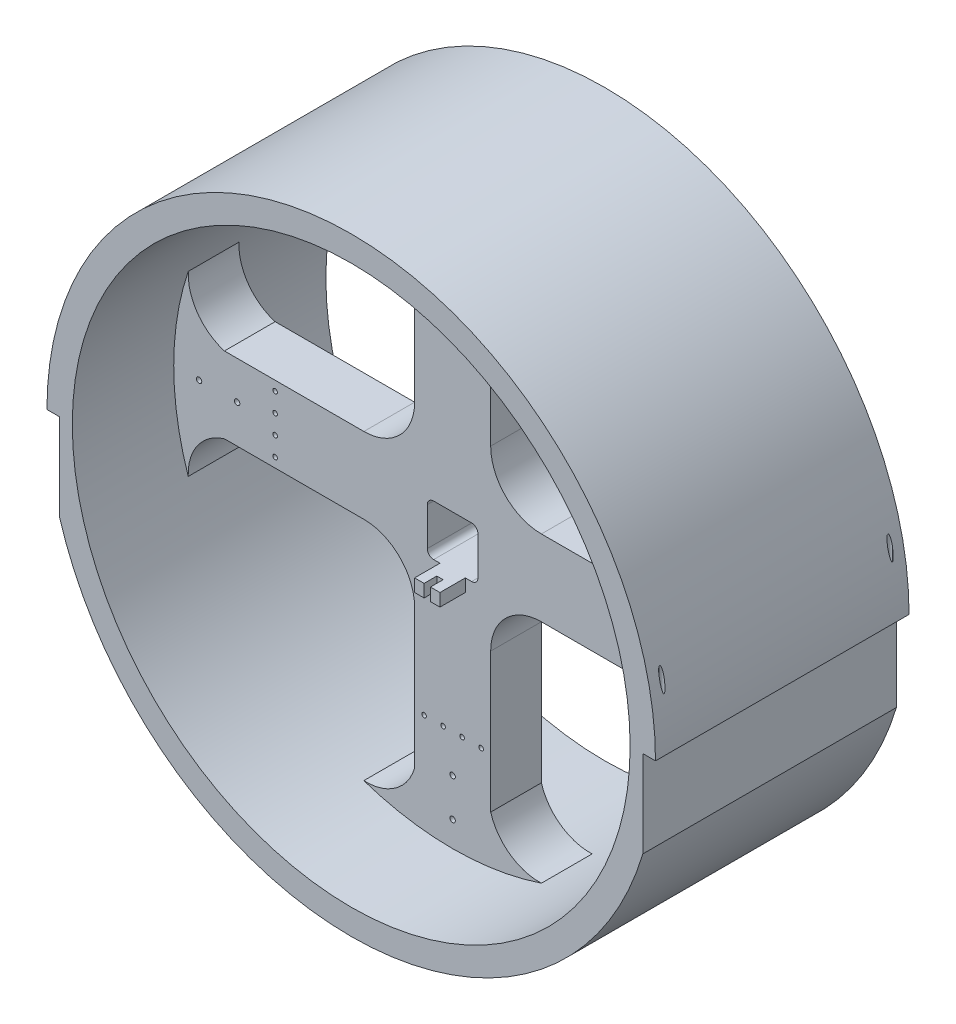
SolidWorks part; units mm, degrees
material "6061 Alloy"
ref_plane "Front Plane" through (0, 0, 0) normal (0, 0, 1) x (1, 0, 0)
ref_plane "Top Plane" through (0, 0, 0) normal (0, 1, 0) x (1, 0, 0)
ref_plane "Right Plane" through (0, 0, 0) normal (1, 0, 0) x (0, 0, -1)
sketch "Sketch1" plane through (0, 0, 0) normal (0, 0, 1) x (1, 0, 0)
  circle A0 centre (0, 0) radius 152.4
  circle A1 centre (0, 0) radius 139.7
  dimension "D1" = 304.8
  dimension "D2" = 279.4
extrude "Boss-Extrude1" add sketch "Sketch1" along normal mid plane 127
sketch "Sketch2" plane through (0, 0, 0) normal (0, 0, 1) x (1, 0, 0)
  line L0 (-114.3, 19.05) -> (-138.7192, 19.05)
  line L1 (-147.1918, -19.05) -> (147.1918, -19.05)
  line L2 (-147.1918, -19.05) -> (-147.1918, 19.05)
  line L3 (-147.1918, 19.05) -> (147.1918, 19.05)
  line L4 (147.1918, -19.05) -> (147.1918, 19.05)
  line L5 (-147.1918, -19.05) -> (147.1918, 19.05) construction
  line L6 (-147.1918, 19.05) -> (147.1918, -19.05) construction
  line L7 (19.05, -143.9568) -> (-19.05, -143.9568)
  line L8 (19.05, -143.9568) -> (19.05, 143.9568)
  line L9 (19.05, 143.9568) -> (-19.05, 143.9568)
  line L10 (-19.05, -143.9568) -> (-19.05, 143.9568)
  line L11 (19.05, -143.9568) -> (-19.05, 143.9568) construction
  line L12 (19.05, 143.9568) -> (-19.05, -143.9568) construction
  line L15 (-44.45, 19.05) -> (-19.05, 19.05)
  line L16 (-19.05, 44.45) -> (-19.05, 19.05)
  line L17 (-132.4254, 44.4927) -> (-143.3503, 19.05)
  line L18 (-143.3503, 19.05) -> (-138.7192, 19.05)
  line L19 (-138.7192, 19.05) -> (-143.3503, 19.05)
  line L20 (-19.05, 114.3) -> (-19.05, 143.9568)
  line L21 (-44.45, 132.4398) -> (-19.05, 143.9568)
  line L22 (44.45, 19.05) -> (19.05, 19.05)
  line L23 (19.05, 44.45) -> (19.05, 19.05)
  line L24 (19.05, 143.3503) -> (19.05, 138.7192)
  line L25 (19.05, 114.3) -> (19.05, 138.7192)
  line L26 (44.4927, 132.4254) -> (19.05, 143.3503)
  line L27 (114.3, 19.05) -> (143.9568, 19.05)
  line L28 (132.4398, 44.45) -> (143.9568, 19.05)
  line L29 (19.05, -44.45) -> (19.05, -19.05)
  line L30 (44.45, -19.05) -> (19.05, -19.05)
  line L31 (143.3503, -19.05) -> (138.7192, -19.05)
  line L32 (114.3, -19.05) -> (138.7192, -19.05)
  line L33 (132.4254, -44.4927) -> (143.3503, -19.05)
  line L34 (19.05, -114.3) -> (19.05, -143.9568)
  line L35 (44.45, -132.4398) -> (19.05, -143.9568)
  line L36 (-44.45, -19.05) -> (-19.05, -19.05)
  line L37 (-19.05, -44.45) -> (-19.05, -19.05)
  line L38 (-19.05, -143.3503) -> (-19.05, -138.7192)
  line L39 (-19.05, -114.3) -> (-19.05, -138.7192)
  line L40 (-44.4927, -132.4254) -> (-19.05, -143.3503)
  line L41 (-114.3, -19.05) -> (-143.9568, -19.05)
  line L42 (-132.4398, -44.45) -> (-143.9568, -19.05)
  arc A1 (-44.45, 19.05) -> (-19.05, 44.45) centre (-44.45, 44.45) ccw
  arc A2 (-114.3, 19.05) -> (-132.4254, 44.4927) centre (-107.0492, 43.3931) cw
  circle A3 centre (0, 0) radius 139.7 construction
  arc A5 (-19.05, 114.3) -> (-44.45, 132.4398) centre (-43.3968, 107.0616) ccw
  arc A6 (19.05, 44.45) -> (44.45, 19.05) centre (44.45, 44.45) ccw
  arc A7 (19.05, 114.3) -> (44.4927, 132.4254) centre (43.3931, 107.0492) cw
  arc A8 (114.3, 19.05) -> (132.4398, 44.45) centre (107.0616, 43.3968) ccw
  arc A9 (44.45, -19.05) -> (19.05, -44.45) centre (44.45, -44.45) ccw
  arc A10 (114.3, -19.05) -> (132.4254, -44.4927) centre (107.0492, -43.3931) cw
  arc A11 (19.05, -114.3) -> (44.45, -132.4398) centre (43.3968, -107.0616) ccw
  arc A12 (-19.05, -44.45) -> (-44.45, -19.05) centre (-44.45, -44.45) ccw
  arc A13 (-19.05, -114.3) -> (-44.4927, -132.4254) centre (-43.3931, -107.0492) cw
  arc A14 (-114.3, -19.05) -> (-132.4398, -44.45) centre (-107.0616, -43.3968) ccw
  point P0 (0, 0)
  point P6 (0, 0)
  point P67 (0, 0)
  dimension "D3" = 25.4
  dimension "D5" = 25.4
  dimension "D1" = 38.1
  dimension "D2" = 38.1
  dimension "D4" = 114.3
  dimension "D6" = 114.3
  dimension "D7" = 4
extrude "Boss-Extrude2" add sketch "Sketch2" along normal mid plane 25.4 contours L1 L10 L3 L2 | L10 L1 L8 L3 | L10 L3 L8 L9 | L8 L1 L4 L3 | L10 L7 L8 L1 | A14 L1 L42 | L10 A13 L40 | A11 L8 L35 | A9 L1 L8 | L1 A10 L33 | A8 L3 L28 | L8 A7 L26 | A5 L10 L21 | L0 A2 L17 L3 | A1 L3 L10 | A6 L8 L3 | A12 L10 L1 region at (-83.1209, 0, 0) region at (-132.2215, 26.1932, 0) region at (-24.7235, 24.7235, 0) region at (0, 81.5034, 0) region at (0, 0, 0) region at (24.7235, 24.7235, 0) region at (83.1209, 0, 0) region at (-24.7235, -24.7235, 0) region at (0, -81.5034, 0) region at (-26.2233, 132.4495, 0) region at (24.7235, -24.7235, 0) region at (-132.4495, -26.2233, 0) region at (132.4495, 26.2233, 0) region at (26.1932, 132.2215, 0) region at (-26.1932, -132.2215, 0) region at (132.2215, -26.1932, 0) region at (26.2233, -132.4495, 0)
sketch "Sketch4" plane through (0, 0, 0) normal (0, 0, 1) x (1, 0, 0)
  line L0 (-12.7, -19.05) -> (-12.7, 6.35)
  line L5 (-12.7, -19.05) -> (12.7, -19.05)
  line L6 (-12.7, 6.35) -> (12.7, 6.35)
  line L7 (12.7, -19.05) -> (12.7, 6.35)
  line L8 (-12.7, -19.05) -> (12.7, 6.35) construction
  line L9 (-12.7, 6.35) -> (12.7, -19.05) construction
  point P1 (0, -6.35)
  dimension "D1" = 25.4
  dimension "D2" = 25.4
  dimension "D3" = 0
  dimension "D4" = 6.35
extrude "Cut-Extrude3" cut sketch "Sketch4" against normal through all both and the other way through all
sketch "Sketch8" plane through (0, 0, 63.5) normal (0, 0, 1) x (1, 0, 0)
  line L0 (-146.05, 0) -> (-163.2527, 0)
  line L1 (-146.05, 0) -> (-146.05, -50.8)
  line L2 (-163.2527, 0) -> (-163.2527, -50.8)
  line L3 (-146.05, -50.8) -> (-163.2527, -50.8)
  circle A0 centre (0, 0) radius 152.4 construction
  dimension "D1" = 50.8
  dimension "D2" = 146.05
extrude "Cut-Extrude5" cut sketch "Sketch8" against normal through all
hole_wizard "#4-40 Tapped Hole2" positions "Sketch21" profile "Sketch22" tap size "#4-40" standard "ANSI Inch" end condition through all
sketch "Sketch21" plane through (0, 0, 0) normal (0, -1, 0) x (-1, 0, 0)
  line L0 (146.05, -63.5) -> (152.4, -63.5) construction
  line L1 (146.05, 63.5) -> (152.4, 63.5) construction
  line L2 (152.4, 63.5) -> (152.4, -63.5) construction
  point P0 (149.225, 57.15)
  point P2 (149.225, -57.15)
  dimension "D1" = 6.35
  dimension "D2" = 6.35
  dimension "D3" = 3.175
  dimension "D4" = 3.175
sketch "Sketch22" plane through (-149.225, 0, -57.15) normal (1, 0, 0) x (0, 0, -1)
  line L0 (0, 0) -> (0, 152.4)
  line L1 (0, 152.4) -> (1.1303, 152.4)
  line L2 (1.1303, 152.4) -> (1.1303, 0)
  line L5 (1.1303, 0) -> (0, 0)
  line L11 (0, -6.35) -> (0, 107.95) construction
  dimension "Thru Tap Drill Dia." = 2.2606
  dimension "Thru Tap Drill Depth" = 152.4
cosmetic thread "Hole Thread7" parameters "D2"=2.8448
cosmetic thread "Hole Thread8" parameters "D2"=2.8448
mirror "Mirror1" about plane through (0, 0, 0) normal (1, 0, 0) of "#4-40 Tapped Hole2", "Cut-Extrude5"
hole_wizard "#4-40 Tapped Hole1" positions "Sketch11" profile "Sketch12" tap size "#4-40" standard "ANSI Inch" end condition through all
sketch "Sketch11" plane through (0, 0, 12.7) normal (0, 0, 1) x (1, 0, 0)
  line L1 (44.45, 19.05) -> (114.3, 19.05) construction
  point P4 (88.9, 14.2875)
  point P6 (88.9, 4.7625)
  point P17 (88.9, -4.7625)
  point P19 (88.9, -14.2875)
  dimension "D1" = 88.9
  dimension "D2" = 88.9
  dimension "D3" = 88.9
  dimension "D4" = 9.525
  dimension "D5" = 88.9
  dimension "D6" = 9.525
  dimension "D7" = 4.7625
  dimension "D8" = 9.525
sketch "Sketch12" plane through (88.9, 14.2875, 12.7) normal (1, 0, 0) x (0, -1, 0)
  line L0 (0, 0) -> (0, 76.2)
  line L1 (0, 76.2) -> (1.1303, 76.2)
  line L2 (1.1303, 76.2) -> (1.1303, 0)
  line L5 (1.1303, 0) -> (0, 0)
  line L11 (0, -6.35) -> (0, 107.95) construction
  dimension "Thru Tap Drill Dia." = 2.2606
  dimension "Thru Tap Drill Depth" = 76.2
cosmetic thread "Hole Thread1" parameters "D2"=2.8448
cosmetic thread "Hole Thread2" parameters "D2"=2.8448
cosmetic thread "Hole Thread3" parameters "D2"=2.8448
cosmetic thread "Hole Thread4" parameters "D2"=2.8448
hole_wizard "#6-32 Tapped Hole1" positions "Sketch13" profile "Sketch14" tap size "#6-32" standard "ANSI Inch" end condition through all
sketch "Sketch13" plane through (0, 0, 12.7) normal (0, 0, 1) x (1, 0, 0)
  point P0 (-107.95, 0)
  point P2 (-127, 0)
  dimension "D1" = 107.95
  dimension "D2" = 19.05
sketch "Sketch14" plane through (-107.95, 0, 12.7) normal (1, 0, 0) x (0, -1, 0)
  line L0 (0, 0) -> (0, 76.2)
  line L1 (0, 76.2) -> (1.3525, 76.2)
  line L2 (1.3525, 76.2) -> (1.3525, 0)
  line L5 (1.3525, 0) -> (0, 0)
  line L11 (0, -6.35) -> (0, 107.95) construction
  dimension "Thru Tap Drill Dia." = 2.7051
  dimension "Thru Tap Drill Depth" = 76.2
cosmetic thread "Hole Thread5" parameters "D2"=3.5052
cosmetic thread "Hole Thread6" parameters "D2"=3.5052
pattern_circular "CirPattern1" count 4 every 90 about axis through (0, 0, 63.5) along (0, 0, 1) of "#6-32 Tapped Hole1"
sketch "Sketch17" plane through (0, 0, 12.7) normal (0, 0, 1) x (1, 0, 0)
  line L0 (-12.7, -19.05) -> (12.7, -19.05) construction
  line L1 (-12.7, 6.35) -> (-12.7, -19.05) construction
  line L2 (-12.7, -15.875) -> (-12.7, -19.05)
  line L3 (-12.7, -19.05) -> (-9.525, -19.05)
  line L4 (12.7, 6.35) -> (-12.7, 6.35) construction
  line L5 (12.7, -19.05) -> (12.7, 6.35) construction
  line L6 (-12.7, 3.175) -> (-12.7, 6.35)
  line L7 (-12.7, 6.35) -> (-9.525, 6.35)
  line L8 (9.525, 6.35) -> (12.7, 6.35)
  line L9 (12.7, 6.35) -> (12.7, 3.175)
  line L10 (12.7, -15.875) -> (12.7, -19.05)
  line L11 (12.7, -19.05) -> (9.525, -19.05)
  arc A0 (-9.525, -19.05) -> (-12.7, -15.875) centre (-9.525, -15.875) cw
  arc A1 (-12.7, 3.175) -> (-9.525, 6.35) centre (-9.525, 3.175) cw
  arc A2 (9.525, 6.35) -> (12.7, 3.175) centre (9.525, 3.175) cw
  arc A3 (9.525, -19.05) -> (12.7, -15.875) centre (9.525, -15.875) ccw
  dimension "D1" = 3.175
  dimension "D4" = 3.175
  dimension "D5" = 3.175
  dimension "D6" = 3.175
  dimension "D12" = 3.175
  dimension "D2" = 3.175
  dimension "D3" = 3.175
  dimension "D7" = 3.175
  dimension "D8" = 3.175
  dimension "D9" = 3.175
  dimension "D10" = 3.175
  dimension "D11" = 3.175
extrude "Boss-Extrude4" add sketch "Sketch17" against normal up to surface (25.4 mm away) up to face at (1.3525, 107.95, -12.7)
sketch "Sketch18" plane through (0, 0, 12.7) normal (0, 0, 1) x (1, 0, 0)
  line L0 (-9.525, -19.05) -> (9.525, -19.05) construction
  line L1 (-6.35, -19.05) -> (6.35, -19.05)
  line L2 (-6.35, -19.05) -> (-6.35, -25.4)
  line L3 (-6.35, -25.4) -> (6.35, -25.4)
  line L4 (6.35, -19.05) -> (6.35, -25.4)
  line L5 (-12.7, 3.175) -> (-12.7, -15.875) construction
  dimension "D1" = 12.7
  dimension "D2" = 6.35
  dimension "D3" = 6.35
extrude "Boss-Extrude5" add sketch "Sketch18" along normal blind 12.7 and the other way blind 38.1
sketch "Sketch19" plane through (0, -19.05, 0) normal (0, 1, 0) x (1, 0, 0)
  line L0 (6.35, -25.4) -> (-6.35, -25.4) construction
  line L1 (-1.5875, -25.4) -> (1.5875, -25.4)
  line L2 (-1.5875, -25.4) -> (-1.5875, -19.05)
  line L3 (-1.5875, -19.05) -> (1.5875, -19.05)
  line L4 (1.5875, -25.4) -> (1.5875, -19.05)
  line L5 (-6.35, -12.7) -> (-6.35, -25.4) construction
  dimension "D1" = 3.175
  dimension "D2" = 4.7625
  dimension "D3" = 6.35
extrude "Cut-Extrude6" cut sketch "Sketch19" against normal up to next
sketch "Sketch20" plane through (0, -19.05, 0) normal (0, 1, 0) x (1, 0, 0)
  line L0 (6.35, 25.4) -> (-6.35, 25.4) construction
  line L1 (1.5875, 25.4) -> (-1.5875, 25.4)
  line L2 (1.5875, 25.4) -> (1.5875, 19.05)
  line L3 (1.5875, 19.05) -> (-1.5875, 19.05)
  line L4 (-1.5875, 25.4) -> (-1.5875, 19.05)
  line L5 (6.35, 25.4) -> (6.35, 12.7) construction
  dimension "D1" = 3.175
  dimension "D2" = 6.35
  dimension "D3" = 4.7625
extrude "Cut-Extrude7" cut sketch "Sketch20" against normal up to next
pattern_circular "CirPattern2" count 4 every 90 about axis through (0, 0, 63.5) along (0, 0, 1) of "#4-40 Tapped Hole1"
